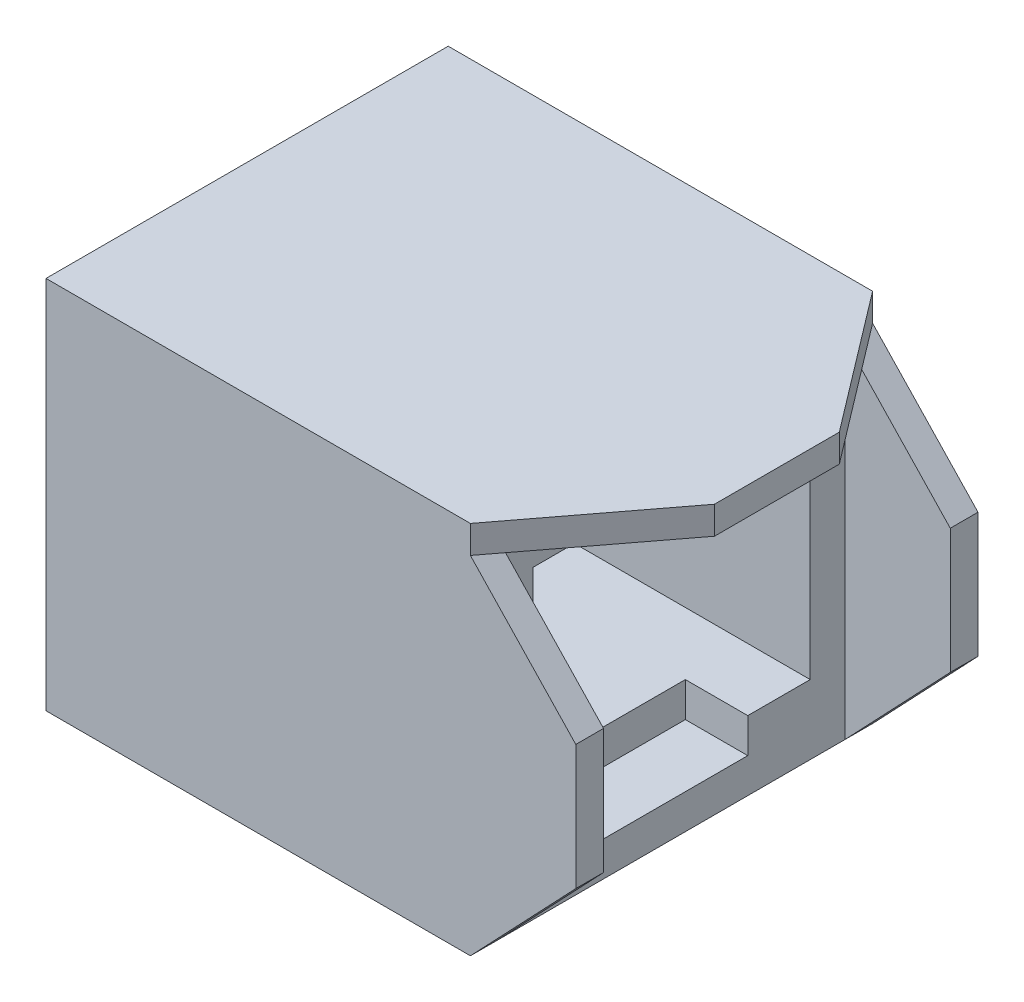
SolidWorks part; units mm, degrees
ref_plane "前视基准面" through (0, 0, 0) normal (0, 0, 1) x (1, 0, 0)
ref_plane "上视基准面" through (0, 0, 0) normal (0, 1, 0) x (1, 0, 0)
ref_plane "右视基准面" through (0, 0, 0) normal (1, 0, 0) x (0, 0, -1)
other "Configuration Table"
sketch "草图1" plane through (0, 0, 0) normal (1, 0, 0) x (0, 0, -1)
  line L0 (0, 0) -> (12.5, 0) construction
  line L1 (12.5, 12.5) -> (-12.5, 12.5)
  line L2 (12.5, 12.5) -> (12.5, -12.5)
  line L3 (12.5, -12.5) -> (-12.5, -12.5)
  line L4 (-12.5, 12.5) -> (-12.5, -12.5)
  line L5 (14.5, 14.5) -> (-14.5, 14.5)
  line L6 (14.5, 14.5) -> (14.5, -14.5)
  line L7 (14.5, -14.5) -> (-14.5, -14.5)
  line L8 (-14.5, 14.5) -> (-14.5, -14.5)
  line L9 (12.5, 0) -> (14.5, 0) construction
  line L10 (0, 0) -> (0, 12.5) construction
  line L11 (0, 12.5) -> (0, 14.5) construction
  line L13 (-10, 9.5) -> (10, 9.5)
  line L14 (-10, 9.5) -> (-10, -7.5)
  line L15 (-10, -7.5) -> (10, -7.5)
  line L16 (10, 9.5) -> (10, -7.5)
  line L18 (-4, -4) -> (4, -4)
  line L19 (-4, -4) -> (-4, 4)
  line L20 (-4, 4) -> (4, 4)
  line L21 (4, -4) -> (4, 4)
  line L22 (-4, -4) -> (4, 4) construction
  line L23 (-4, 4) -> (4, -4) construction
  point P20 (0, 9.5)
  dimension "D1" = 25
  dimension "D2" = 29
  dimension "D3" = 20
  dimension "D4" = 17
  dimension "D5" = 9.5
  dimension "D6" = 8
extrude "凸台-拉伸1" add sketch "草图1" along normal blind 36.2 contours L5 L8 L7 L6 | L1 L4 L3 L2
extrude "凸台-拉伸2" add sketch "草图1<3>" along normal blind 28.6 contours L1 L4 L3 L2 | L13 L16 L15 L14
sketch "草图1<3>" plane through (0, 0, 0) normal (1, 0, 0) x (0, 0, -1) same geometry as "草图1"
extrude "凸台-拉伸3" add sketch "草图1<4>" against normal blind 2 contours L6 L7 L8 L5
sketch "草图1<4>" plane through (0, 0, 0) normal (1, 0, 0) x (0, 0, -1) same geometry as "草图1"
extrude "凸台-拉伸4" add sketch "草图1<5>" along normal blind 1.1 contours L13 L16 L15 L14 | L20 L21 L18 L19
sketch "草图1<5>" plane through (0, 0, 0) normal (1, 0, 0) x (0, 0, -1) same geometry as "草图1"
sketch "草图4" plane through (0, 0, 14.5) normal (0, 0, 1) x (1, 0, 0)
  line L0 (-2, -12.5) -> (28.6, -12.5)
  line L1 (-2, 14.5) -> (-2, -14.5) construction
  line L4 (28.6, -12.5) -> (36.2, -4.5)
  line L5 (36.2, 14.5) -> (36.2, -14.5) construction
  line L6 (36.2, -4.5) -> (36.2, -14.5)
  line L10 (36.2, -14.5) -> (-2, -14.5)
  line L11 (-2, -14.5) -> (-2, -12.5)
  line L14 (36.2, 12.5) -> (28.6, 12.5)
  line L15 (28.6, 12.5) -> (36.2, 4.5)
  line L16 (36.2, 4.5) -> (36.2, 12.5)
  line L17 (36.2, 14.5) -> (-2, 14.5) construction
  line L18 (28.6, -12.5) -> (36.2, -12.5) construction
  dimension "D1" = 30.6
  dimension "D2" = 2
  dimension "D3" = 10
  dimension "D4" = 8
  dimension "D5" = 30.6
  dimension "D6" = 2
  dimension "D7" = 7.6
extrude "切除-拉伸1" cut sketch "草图4" against normal through all
sketch "草图6" plane through (0, 14.5, 0) normal (0, 1, 0) x (1, 0, 0)
  line L0 (28.6, 14.5) -> (36.2, 14.5)
  line L1 (36.2, 14.5) -> (-2, 14.5) construction
  line L2 (36.2, 14.5) -> (36.2, 4.5)
  line L3 (36.2, 14.5) -> (36.2, -14.5) construction
  line L4 (36.2, 4.5) -> (28.6, 14.5)
  line L5 (36.2, 0) -> (-2, 0) construction
  line L6 (-2, 14.5) -> (-2, -14.5) construction
  line L7 (36.2, -14.5) -> (36.2, -4.5)
  line L8 (28.6, -14.5) -> (36.2, -14.5)
  line L9 (36.2, -4.5) -> (28.6, -14.5)
  dimension "D1" = 10
  dimension "D2" = 30.6
  dimension "D3" = 7.6
extrude "切除-拉伸2" cut sketch "草图6" against normal up to next
sketch "草图7" plane through (0, 0, 14.5) normal (0, 0, 1) x (1, 0, 0)
  line L0 (-2, 14.5) -> (-2, -12.5) construction
  line L1 (48, 10.5) -> (-2, 10.5)
  line L2 (48, 10.5) -> (48, 9.5)
  line L3 (48, 9.5) -> (-2, 9.5)
  line L4 (-2, 10.5) -> (-2, 9.5)
  line L5 (28.6, 14.5) -> (-2, 14.5) construction
  dimension "D1" = 1
  dimension "D2" = 50
  dimension "D3" = 5
extrude "切除-拉伸3" cut sketch "草图7" against normal blind 2 and the other way blind 2 from surface starting at plane "前视基准面"
hole_wizard "孔1" positions "草图9" profile "草图10" legacy
sketch "草图9" plane through (0, -12.5, 0) normal (0, -1, 0) x (-1, 0, 0)
  line L0 (2, 14.5) -> (2, -14.5) construction
  point P0 (-1, 0)
  dimension "D1" = 3
sketch "草图10" plane through (1, -12.5, 0) normal (1, 0, 0) x (0, 0, -1)
  line L0 (0, 0) -> (0, 4)
  line L1 (0, 4) -> (0.9, 4)
  line L2 (0.9, 4) -> (0.9, 0)
  line L3 (0.9, 0) -> (0, 0)
  line L4 (0, 110) -> (0, -10) construction
  dimension "直径" = 1.8
  dimension "深度" = 4
sketch "草图11" plane through (28.6, 0, 0) normal (1, 0, 0) x (0, 0, -1)
  line L0 (-10, -7.5) -> (10, -7.5) construction
  line L1 (-5.5, -7.5) -> (5.5, -7.5)
  line L2 (-5.5, -7.5) -> (-5.5, -10)
  line L3 (-5.5, -10) -> (5.5, -10)
  line L4 (5.5, -7.5) -> (5.5, -10)
  line L5 (0, 0) -> (0, -7.5)
  line M13 (10, -7.5) -> (-10, -7.5)
  dimension "D1" = 2.5
  dimension "D2" = 11
extrude "切除-拉伸4" cut sketch "草图11" against normal blind 4.5 contours L4 L1 L2 L3 M13 region at (28.6, -8.75, 0)
